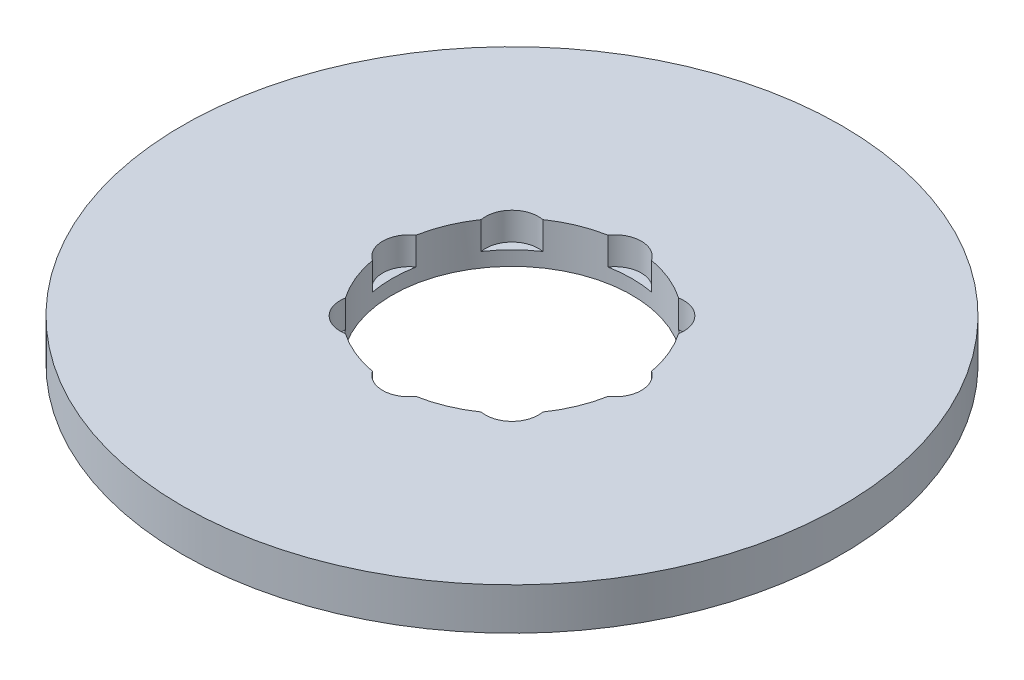
SolidWorks part; units mm, degrees
ref_plane "Front Plane" through (0, 0, 0) normal (0, 0, 1) x (1, 0, 0)
ref_plane "Top Plane" through (0, 0, 0) normal (0, 1, 0) x (1, 0, 0)
ref_plane "Right Plane" through (0, 0, 0) normal (1, 0, 0) x (0, 0, -1)
sketch "Sketch1" plane through (0, 0, 0) normal (0, 1, 0) x (1, 0, 0)
  circle A0 centre (0, 0) radius 55
  dimension "FLANGE_OD" = 110
extrude "Boss-Extrude1" add sketch "Sketch1" along normal blind 7
sketch "Sketch2" plane through (0, 0, 0) normal (0, 1, 0) x (1, 0, 0)
  circle A0 centre (0, 0) radius 20
  dimension "BORE_D" = 40
extrude "Cut-Extrude1" cut sketch "Sketch2" along normal through all
sketch "Sketch3" plane through (0, 7, 0) normal (0, 1, 0) x (1, 0, 0)
  circle A0 centre (0, 0) radius 17.1753 construction
  circle A1 centre (-17.1753, 0) radius 4.4071
  dimension "BOLT_D" = 8.8141
  dimension "BOLT_PCD" = 34.3507
extrude "Cut-Extrude2" cut sketch "Sketch3" against normal blind 4.6068
pattern_circular "CirPattern1" count 8 over 360 about axis through (0, 0, 0) along (0, 1, 0) of "Cut-Extrude2"
